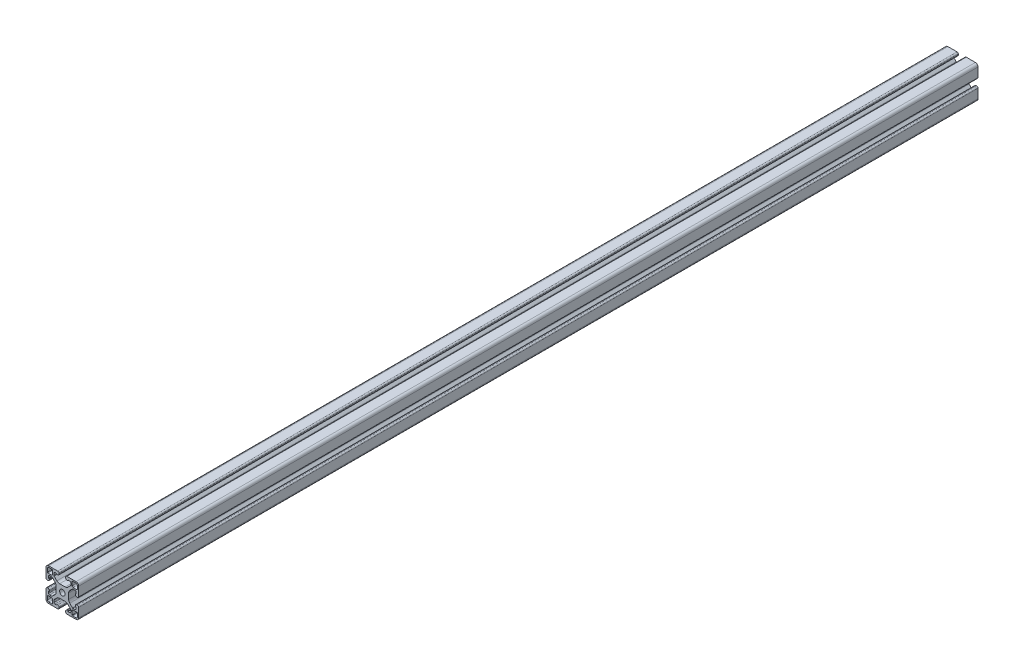
SolidWorks part; units mm, degrees
material "6005A-T61 Aluminum"
ref_plane "Front Plane" through (0, 0, 0) normal (0, 0, 1) x (1, 0, 0)
ref_plane "Top Plane" through (0, 0, 0) normal (0, 1, 0) x (1, 0, 0)
ref_plane "Right Plane" through (0, 0, 0) normal (1, 0, 0) x (0, 0, -1)
sketch "Sketch2" plane through (0, 0, 0) normal (0, 0, 1) x (1, 0, 0)
  line L0 (-16.82, 20) -> (-5.635, 20)
  line L1 (-3.379, 7.68) -> (3.379, 7.68)
  line L2 (-10.285, 12.9871) -> (-10.285, 15.5)
  line L3 (10.285, 12.9871) -> (10.285, 15.5)
  line L4 (4.065, 17.51) -> (4.065, 18.43)
  line L5 (-4.065, 17.51) -> (-4.065, 18.43)
  line L6 (-6.855, 15.94) -> (-5.635, 15.94)
  line L7 (5.635, 15.94) -> (6.855, 15.94)
  line L8 (5.635, 20) -> (16.82, 20)
  line L9 (6.855, 16.77) -> (9.015, 16.77)
  line L10 (-9.015, 16.77) -> (-6.855, 16.77)
  line L11 (-6.855, 15.94) -> (-6.855, 16.77)
  line L12 (6.855, 15.94) -> (6.855, 16.77)
  line L13 (-6.7378, 9.0712) -> (-10.0243, 12.3578)
  line L14 (6.7378, 9.0712) -> (10.0243, 12.3578)
  line L15 (-16.78, 18.35) -> (-12.575, 18.35)
  line L16 (-18.35, 16.78) -> (-18.35, 12.575)
  line L17 (-11.935, 13.205) -> (-11.935, 17.71)
  line L18 (-13.205, 11.935) -> (-17.71, 11.935)
  line L19 (-7.68, -3.379) -> (-7.68, 3.379)
  line L20 (-20, -16.82) -> (-20, -5.635)
  line L21 (-18.35, -16.78) -> (-18.35, -12.575)
  line L22 (-20, 5.635) -> (-20, 16.82)
  line L23 (-15.94, -6.855) -> (-15.94, -5.635)
  line L24 (-16.77, -9.015) -> (-16.77, -6.855)
  line L25 (-15.94, 5.635) -> (-15.94, 6.855)
  line L26 (-16.77, 6.855) -> (-16.77, 9.015)
  line L27 (-9.0712, 6.7378) -> (-12.3578, 10.0243)
  line L28 (-9.0712, -6.7378) -> (-12.3578, -10.0243)
  line L29 (-17.51, -4.065) -> (-18.43, -4.065)
  line L30 (-17.51, 4.065) -> (-18.43, 4.065)
  line L31 (-12.9871, 10.285) -> (-15.5, 10.285)
  line L32 (-15.94, 6.855) -> (-16.77, 6.855)
  line L33 (-12.9871, -10.285) -> (-15.5, -10.285)
  line L34 (-13.205, -11.935) -> (-17.71, -11.935)
  line L35 (-15.94, -6.855) -> (-16.77, -6.855)
  line L36 (-16.78, -18.35) -> (-12.575, -18.35)
  line L37 (-11.935, -13.205) -> (-11.935, -17.71)
  line L38 (3.379, -7.68) -> (-3.379, -7.68)
  line L39 (16.82, -20) -> (5.635, -20)
  line L40 (16.78, -18.35) -> (12.575, -18.35)
  line L41 (-5.635, -20) -> (-16.82, -20)
  line L42 (6.855, -15.94) -> (5.635, -15.94)
  line L43 (9.015, -16.77) -> (6.855, -16.77)
  line L44 (-5.635, -15.94) -> (-6.855, -15.94)
  line L45 (-6.855, -16.77) -> (-9.015, -16.77)
  line L46 (-6.7378, -9.0712) -> (-10.0243, -12.3578)
  line L47 (6.7378, -9.0712) -> (10.0243, -12.3578)
  line L48 (4.065, -17.51) -> (4.065, -18.43)
  line L49 (-4.065, -17.51) -> (-4.065, -18.43)
  line L50 (-10.285, -12.9871) -> (-10.285, -15.5)
  line L51 (-6.855, -15.94) -> (-6.855, -16.77)
  line L52 (10.285, -12.9871) -> (10.285, -15.5)
  line L53 (11.935, -13.205) -> (11.935, -17.71)
  line L54 (6.855, -15.94) -> (6.855, -16.77)
  line L55 (18.35, -16.78) -> (18.35, -12.575)
  line L56 (13.205, -11.935) -> (17.71, -11.935)
  line L57 (7.68, 3.379) -> (7.68, -3.379)
  line L58 (20, 16.82) -> (20, 5.635)
  line L59 (18.35, 16.78) -> (18.35, 12.575)
  line L60 (20, -5.635) -> (20, -16.82)
  line L61 (15.94, 6.855) -> (15.94, 5.635)
  line L62 (16.77, 9.015) -> (16.77, 6.855)
  line L63 (15.94, -5.635) -> (15.94, -6.855)
  line L64 (16.77, -6.855) -> (16.77, -9.015)
  line L65 (9.0712, -6.7378) -> (12.3578, -10.0243)
  line L66 (9.0712, 6.7378) -> (12.3578, 10.0243)
  line L67 (17.51, 4.065) -> (18.43, 4.065)
  line L68 (17.51, -4.065) -> (18.43, -4.065)
  line L69 (12.9871, -10.285) -> (15.5, -10.285)
  line L70 (15.94, -6.855) -> (16.77, -6.855)
  line L71 (12.9871, 10.285) -> (15.5, 10.285)
  line L72 (13.205, 11.935) -> (17.71, 11.935)
  line L73 (15.94, 6.855) -> (16.77, 6.855)
  line L74 (16.78, 18.35) -> (12.575, 18.35)
  line L75 (11.935, 13.205) -> (11.935, 17.71)
  circle A0 centre (0, 0) radius 3.405
  arc A1 (-6.7378, 9.0712) -> (-3.379, 7.68) centre (-3.379, 12.43) ccw
  arc A2 (3.379, 7.68) -> (6.7378, 9.0712) centre (3.379, 12.43) ccw
  arc A3 (10.0243, 12.3578) -> (10.285, 12.9871) centre (9.395, 12.9871) ccw
  arc A4 (-10.285, 12.9871) -> (-10.0243, 12.3578) centre (-9.395, 12.9871) ccw
  arc A5 (-9.015, 16.77) -> (-10.285, 15.5) centre (-9.015, 15.5) ccw
  arc A6 (10.285, 15.5) -> (9.015, 16.77) centre (9.015, 15.5) ccw
  arc A7 (4.065, 17.51) -> (5.635, 15.94) centre (5.635, 17.51) ccw
  arc A8 (5.635, 20) -> (4.065, 18.43) centre (5.635, 18.43) ccw
  arc A9 (-4.065, 18.43) -> (-5.635, 20) centre (-5.635, 18.43) ccw
  arc A10 (-5.635, 15.94) -> (-4.065, 17.51) centre (-5.635, 17.51) ccw
  arc A11 (-16.78, 18.35) -> (-18.35, 16.78) centre (-16.78, 16.78) ccw
  arc A12 (-11.935, 17.71) -> (-12.575, 18.35) centre (-12.575, 17.71) ccw
  arc A13 (-18.35, 12.575) -> (-17.71, 11.935) centre (-17.71, 12.575) ccw
  arc A14 (-13.205, 11.935) -> (-11.935, 13.205) centre (-13.205, 13.205) ccw
  arc A15 (-18.35, -16.78) -> (-16.78, -18.35) centre (-16.78, -16.78) ccw
  arc A16 (-20, 5.635) -> (-18.43, 4.065) centre (-18.43, 5.635) ccw
  arc A17 (-15.94, -5.635) -> (-17.51, -4.065) centre (-17.51, -5.635) ccw
  arc A18 (-16.77, -9.015) -> (-15.5, -10.285) centre (-15.5, -9.015) ccw
  arc A19 (-7.68, 3.379) -> (-9.0712, 6.7378) centre (-12.43, 3.379) ccw
  arc A20 (-9.0712, -6.7378) -> (-7.68, -3.379) centre (-12.43, -3.379) ccw
  arc A21 (-18.43, -4.065) -> (-20, -5.635) centre (-18.43, -5.635) ccw
  arc A22 (-17.51, 4.065) -> (-15.94, 5.635) centre (-17.51, 5.635) ccw
  arc A23 (-15.5, 10.285) -> (-16.77, 9.015) centre (-15.5, 9.015) ccw
  arc A24 (-12.3578, 10.0243) -> (-12.9871, 10.285) centre (-12.9871, 9.395) ccw
  arc A25 (-11.935, -13.205) -> (-13.205, -11.935) centre (-13.205, -13.205) ccw
  arc A26 (-17.71, -11.935) -> (-18.35, -12.575) centre (-17.71, -12.575) ccw
  arc A27 (-12.9871, -10.285) -> (-12.3578, -10.0243) centre (-12.9871, -9.395) ccw
  arc A28 (-12.575, -18.35) -> (-11.935, -17.71) centre (-12.575, -17.71) ccw
  arc A29 (16.78, -18.35) -> (18.35, -16.78) centre (16.78, -16.78) ccw
  arc A30 (-5.635, -20) -> (-4.065, -18.43) centre (-5.635, -18.43) ccw
  arc A31 (5.635, -15.94) -> (4.065, -17.51) centre (5.635, -17.51) ccw
  arc A32 (9.015, -16.77) -> (10.285, -15.5) centre (9.015, -15.5) ccw
  arc A33 (-3.379, -7.68) -> (-6.7378, -9.0712) centre (-3.379, -12.43) ccw
  arc A34 (6.7378, -9.0712) -> (3.379, -7.68) centre (3.379, -12.43) ccw
  arc A35 (4.065, -18.43) -> (5.635, -20) centre (5.635, -18.43) ccw
  arc A36 (-4.065, -17.51) -> (-5.635, -15.94) centre (-5.635, -17.51) ccw
  arc A37 (-10.285, -15.5) -> (-9.015, -16.77) centre (-9.015, -15.5) ccw
  arc A38 (-10.0243, -12.3578) -> (-10.285, -12.9871) centre (-9.395, -12.9871) ccw
  arc A39 (13.205, -11.935) -> (11.935, -13.205) centre (13.205, -13.205) ccw
  arc A40 (11.935, -17.71) -> (12.575, -18.35) centre (12.575, -17.71) ccw
  arc A41 (10.285, -12.9871) -> (10.0243, -12.3578) centre (9.395, -12.9871) ccw
  arc A42 (18.35, -12.575) -> (17.71, -11.935) centre (17.71, -12.575) ccw
  arc A43 (18.35, 16.78) -> (16.78, 18.35) centre (16.78, 16.78) ccw
  arc A44 (20, -5.635) -> (18.43, -4.065) centre (18.43, -5.635) ccw
  arc A45 (15.94, 5.635) -> (17.51, 4.065) centre (17.51, 5.635) ccw
  arc A46 (16.77, 9.015) -> (15.5, 10.285) centre (15.5, 9.015) ccw
  arc A47 (7.68, -3.379) -> (9.0712, -6.7378) centre (12.43, -3.379) ccw
  arc A48 (9.0712, 6.7378) -> (7.68, 3.379) centre (12.43, 3.379) ccw
  arc A49 (18.43, 4.065) -> (20, 5.635) centre (18.43, 5.635) ccw
  arc A50 (17.51, -4.065) -> (15.94, -5.635) centre (17.51, -5.635) ccw
  arc A51 (15.5, -10.285) -> (16.77, -9.015) centre (15.5, -9.015) ccw
  arc A52 (12.3578, -10.0243) -> (12.9871, -10.285) centre (12.9871, -9.395) ccw
  arc A53 (11.935, 13.205) -> (13.205, 11.935) centre (13.205, 13.205) ccw
  arc A54 (17.71, 11.935) -> (18.35, 12.575) centre (17.71, 12.575) ccw
  arc A55 (12.9871, 10.285) -> (12.3578, 10.0243) centre (12.9871, 9.395) ccw
  arc A56 (12.575, 18.35) -> (11.935, 17.71) centre (12.575, 17.71) ccw
  arc A57 (20, 16.82) -> (16.82, 20) centre (16.82, 16.82) ccw
  arc A58 (-16.82, 20) -> (-20, 16.82) centre (-16.82, 16.82) ccw
  arc A59 (-20, -16.82) -> (-16.82, -20) centre (-16.82, -16.82) ccw
  arc A60 (16.82, -20) -> (20, -16.82) centre (16.82, -16.82) ccw
extrude "Extrude1" add sketch "Sketch2" along normal mid plane 1100
ref_axis "Hole RS" through (0, 0, 550) along (0, 0, -1)
ref_plane "Plane R" through (0, 0, 0) normal (-1, 0, 0) x (0, 0, 1)
ref_plane "Plane S" through (0, 0, 0) normal (0, 1, 0) x (1, 0, 0)
ref_plane "Left End Plane" through (0, 0, 550) normal (0, 0, 1) x (1, 0, 0)
ref_plane "Right End Plane" through (0, 0, -550) normal (0, 0, -1) x (-1, 0, 0)
